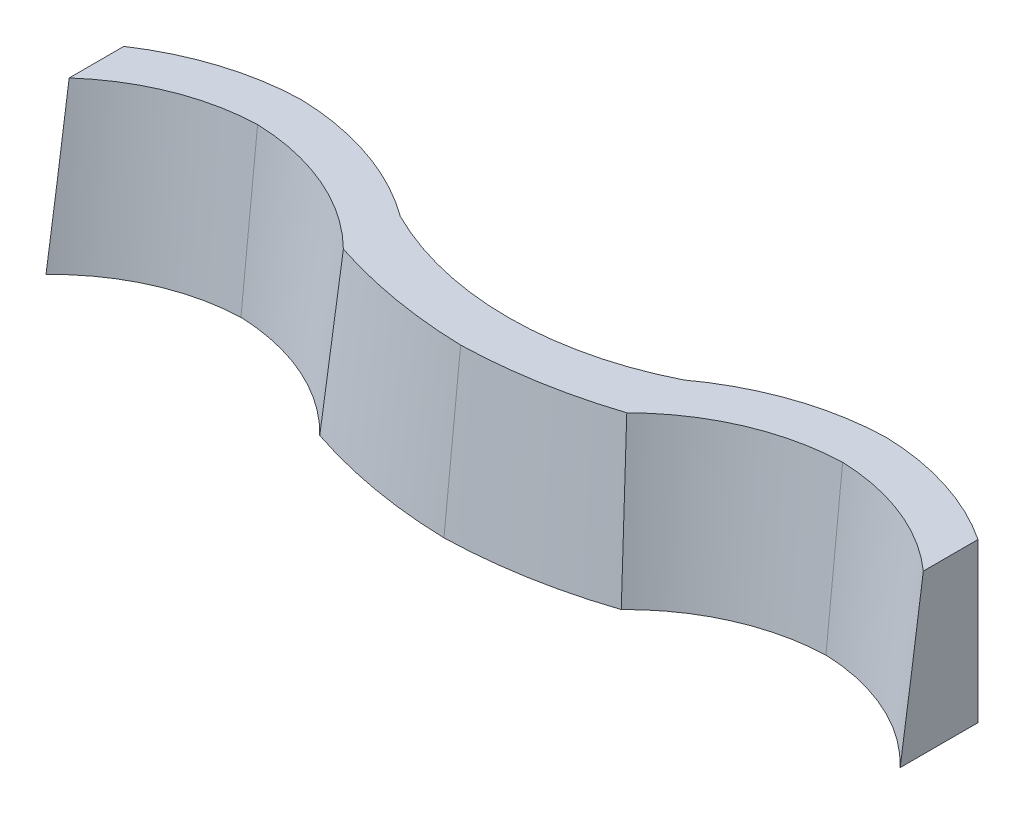
SolidWorks part; units mm, degrees
ref_plane "Front Plane" through (0, 0, 0) normal (0, 0, 1) x (1, 0, 0)
ref_plane "Top Plane" through (0, 0, 0) normal (0, 1, 0) x (1, 0, 0)
ref_plane "Right Plane" through (0, 0, 0) normal (1, 0, 0) x (0, 0, -1)
sketch "Sketch1" plane through (0, 0, 0) normal (0, 1, 0) x (1, 0, 0)
  line L0 (-110, -30) -> (-110, -41.2422) construction
  line L1 (-39.8399, -30) -> (34.8399, -30) construction
  line L2 (110, -30) -> (110, -41.2422) construction
  line L3 (0, -142.6423) -> (0, 36.4059) construction
  line L4 (0, -100) -> (0, 70) construction
  line L5 (-42.9151, -50) -> (42.9151, -50) construction
  line L6 (-110, -41.2422) -> (-39.8399, -43.9889) construction
  line L7 (39.8399, -43.9889) -> (110, -41.2422) construction
  line L8 (-110, -30) -> (-39.8399, -30) construction
  line L9 (110, -30) -> (34.8399, -30) construction
  line L10 (-39.8399, -30) -> (-39.8399, -43.9889) construction
  line L11 (34.8399, -30) -> (39.8399, -43.9889) construction
  arc A0 (-39.8399, -30) -> (34.8399, -30) centre (-2.5, 38.0274) ccw construction
  arc A1 (-39.8399, -43.9889) -> (0, -50) centre (-1.9011, 72.4289) ccw construction
  arc A2 (39.8399, -43.9889) -> (0, -50) centre (1.9011, 72.4289) cw construction
  dimension "D1" = 77.6015
  dimension "D2" = 122.4436
  dimension "D3" = 34.8399
  dimension "D4" = 70.1601
  dimension "D5" = 70.1601
  dimension "D6" = 92.242
  dimension "D7" = 13.9889
ref_plane "Bottom Of Chassis" through (0, -15, 0) normal (0, 1, 0) x (1, 0, 0)
ref_plane "Top of Chassis" through (0, 24, 0) normal (0, 1, 0) x (1, 0, 0)
sketch "Sketch3" plane through (0, 24, 0) normal (0, 1, 0) x (1, 0, 0)
  line L4 (110, -30) -> (110, -41.2422)
  line L6 (-71.9147, -28) -> (-71.9147, -17.3273) construction
  line L7 (0, -50) -> (0, -57.8303) construction
  line L8 (0, -142.6423) -> (0, 36.4059) construction
  line L9 (105, -41.2425) -> (105, -27.799)
  line L10 (-88.5863, -28) -> (-55.2431, -28) construction
  line L11 (-105, -41.2425) -> (-105, -27.799)
  line L12 (-110, 50) -> (-110, -30) construction
  line L13 (71.9147, -28) -> (71.9147, -17.3273) construction
  arc A0 (-34.8399, -30) -> (34.8399, -30) centre (0, 39.341) ccw
  arc A1 (0, -50) -> (34.8399, -43.9889) centre (-3.1802, 72.4023) ccw
  arc A2 (-34.8399, -43.9889) -> (-71.9147, -28) centre (-73.6989, -83.1159) ccw
  arc A3 (-71.9147, -28) -> (-105, -41.2425) centre (-70.2175, -80.192) ccw
  arc A4 (71.9147, -28) -> (105, -41.2425) centre (70.2175, -80.192) cw
  arc A5 (71.9147, -17.3273) -> (105, -27.799) centre (70.2175, -80.192) cw
  arc A6 (-34.8399, -30) -> (-71.9147, -17.3273) centre (-73.6989, -83.1159) ccw
  arc A7 (-71.9147, -17.3273) -> (-105, -27.799) centre (-70.2175, -80.192) ccw
  arc A8 (-71.9147, -17.3273) -> (-112.1058, -33.2855) centre (-70.2175, -80.192) ccw construction
  arc A9 (-29.276, -34.5574) -> (-71.9147, -17.3273) centre (-73.6989, -83.1159) ccw construction
  arc A10 (34.8399, -30) -> (71.9147, -17.3273) centre (73.6989, -83.1159) cw
  arc A11 (34.8399, -43.9889) -> (71.9147, -28) centre (73.6989, -83.1159) cw
  arc A16 (0, -50) -> (39.8399, -43.9889) centre (1.9011, 72.4289) ccw construction
  arc A18 (-34.8399, -43.9889) -> (0, -50) centre (3.1802, 72.4023) ccw
  arc A19 (-39.8399, -43.9889) -> (0, -50) centre (-1.9011, 72.4289) ccw construction
  arc A20 (-39.8399, -30) -> (34.8399, -30) centre (-2.5, 38.0274) ccw construction
  arc A21 (-29.276, -34.5574) -> (0, -39.3281) centre (3.1802, 72.4023) ccw construction
  arc A22 (0, -39.3281) -> (31.5274, -33.8482) centre (-3.1802, 72.4023) ccw construction
  point P15 (0, -50.6571)
  dimension "D1" = 10.668
extrude "Boss-Extrude1" add sketch "Sketch3" against normal up to surface (39 mm away) contours A2 A18 A1 A11 A4 L9 L4 A5 A10 A0 A6 A7 L11 A3 region at (90.4117, 24, 29.7385) up to plane "Bottom Of Chassis"
draft "Draft2" type of draft neutral plane draft angle 6 faces to draft 6 face at (89.0397, 4.5, 33.1664) face at (52.6193, 4.5, 34.2369) face at (17.529, 4.5, 47.6265) face at (-89.0397, 4.5, 33.1664) face at (-52.6193, 4.5, 34.2369) face at (-17.529, 4.5, 47.6265) neutral plane through (0, 24, 0) neutral plane normal (0, 1, 0) parameters "D1"=6
